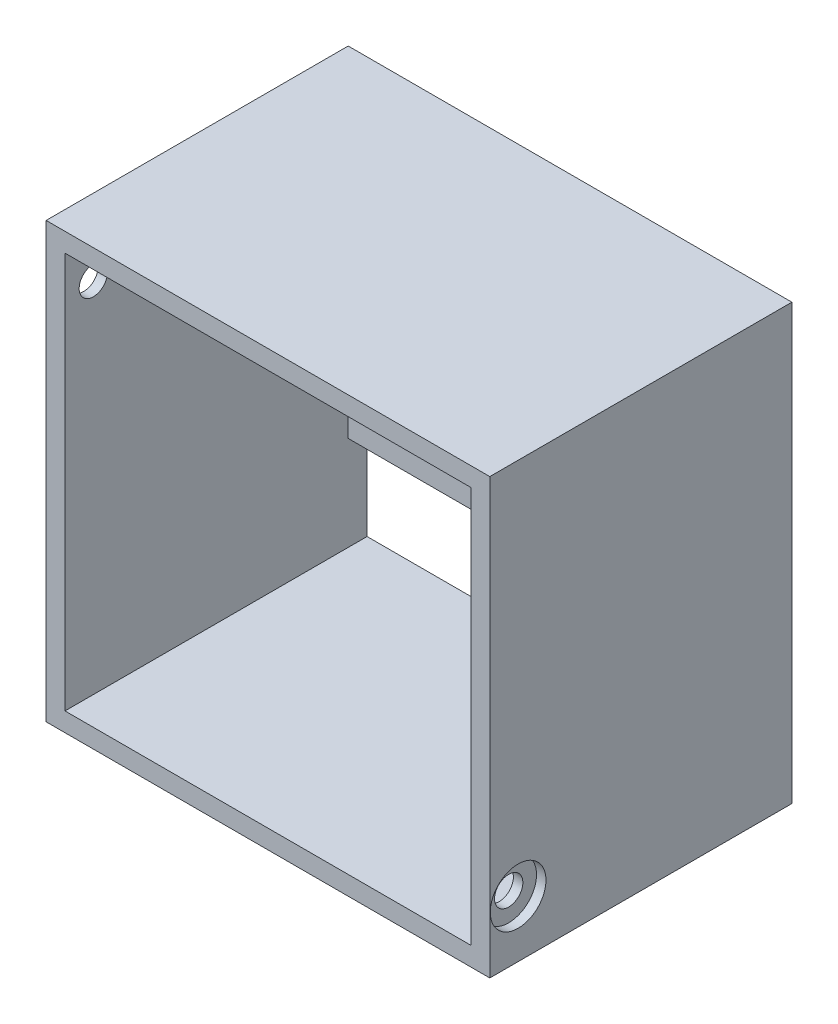
SolidWorks part; units mm, degrees
ref_plane "Front Plane" through (0, 0, 0) normal (0, 0, 1) x (1, 0, 0)
ref_plane "Top Plane" through (0, 0, 0) normal (0, 1, 0) x (1, 0, 0)
ref_plane "Right Plane" through (0, 0, 0) normal (1, 0, 0) x (0, 0, -1)
sketch "Sketch1" plane through (0, 0, 0) normal (0, 0, 1) x (1, 0, 0)
  line L1 (-39.6754, 60.7228) -> (3.3246, 60.7228)
  line L2 (-39.6754, 60.7228) -> (-39.6754, 18.7228)
  line L3 (-39.6754, 18.7228) -> (3.3246, 18.7228)
  line L4 (3.3246, 60.7228) -> (3.3246, 18.7228)
  line L9 (-41.6754, 62.7228) -> (5.3246, 62.7228)
  line L10 (-41.6754, 62.7228) -> (-41.6754, 16.7228)
  line L11 (-41.6754, 16.7228) -> (5.3246, 16.7228)
  line L12 (5.3246, 62.7228) -> (5.3246, 16.7228)
  dimension "D1" = 42
  dimension "D2" = 43
  dimension "D3" = 2
  dimension "D4" = 2
  dimension "D5" = 2
  dimension "D6" = 2
extrude "Walls" add sketch "Sketch1" along normal blind 30
extrude "Back" add sketch "Sketch1<2>" against normal blind 2 contours L4 L1 L2 L3 | L12 L9 L10 L11 L1 L4 L3 L2 region at (-18.1754, 39.7228, 0) region at (-18.1754, 62.0651, 0)
sketch "Sketch1<2>" plane through (0, 0, 0) normal (0, 0, 1) x (1, 0, 0) same geometry as "Sketch1"
sketch "Sketch2" plane through (0, 0, -2) normal (0, 0, -1) x (-1, 0, 0)
  line L0 (41.6754, 16.7228) -> (-5.3246, 16.7228) construction
  line L1 (24.6754, 28.7228) -> (39.6754, 28.7228)
  line L2 (24.6754, 28.7228) -> (24.6754, 18.7228)
  line L3 (24.6754, 18.7228) -> (39.6754, 18.7228)
  line L4 (39.6754, 28.7228) -> (39.6754, 18.7228)
  line L5 (41.6754, 62.7228) -> (41.6754, 16.7228) construction
  dimension "D1" = 10
  dimension "D2" = 15
  dimension "D3" = 2
  dimension "D4" = 2
extrude "Cable" cut sketch "Sketch2" against normal blind 2
sketch "Sketch3" plane through (-41.6754, 0, 0) normal (-1, 0, 0) x (0, 0, 1)
  line L0 (-2, 62.7228) -> (-2, 16.7228) construction
  line L1 (-2, 39.7228) -> (30, 39.7228) construction
  line L2 (30, 62.7228) -> (30, 16.7228) construction
  circle A0 centre (27, 56.7125) radius 1.5
  circle A1 centre (27, 56.7125) radius 2.95
  circle A2 centre (27, 22.733) radius 1.5
  circle A3 centre (27, 22.733) radius 2.95
  dimension "D1" = 3
  dimension "D2" = 5.9
  dimension "D3" = 29
extrude "SetScrew1" cut sketch "Sketch3" against normal blind 2 contours A0 region at (-41.6754, 56.7125, 27)
extrude "SetScrew2" cut sketch "Sketch3<6>" against normal blind 1 contours A1 A0 region at (-41.6754, 56.7125, 24.1334)
sketch "Sketch3<6>" plane through (-41.6754, 0, 0) normal (-1, 0, 0) x (0, 0, 1) same geometry as "Sketch3"
extrude "SetScrew3" cut sketch "Sketch3<7>" along normal blind 1 from surface contours A3 A2 region at (-41.6754, 22.733, 24.1334) starting at face at (5.3246, 39.7228, 14)
sketch "Sketch3<7>" plane through (-41.6754, 0, 0) normal (-1, 0, 0) x (0, 0, 1) same geometry as "Sketch3"
extrude "SetScrew4" cut sketch "Sketch3<8>" along normal blind 2 from surface contours A2 region at (-41.6754, 22.733, 27) starting at face at (5.3246, 19.783, 27)
sketch "Sketch3<8>" plane through (-41.6754, 0, 0) normal (-1, 0, 0) x (0, 0, 1) same geometry as "Sketch3"
sketch "Sketch4" plane through (0, 0, -2) normal (0, 0, -1) x (-1, 0, 0)
  line L0 (-5.3246, 39.7228) -> (41.6754, 39.7228) construction
  line L1 (-5.3246, 62.7228) -> (-5.3246, 16.7228) construction
  line L2 (41.6754, 62.7228) -> (41.6754, 16.7228) construction
  line L3 (18.1754, 62.7228) -> (18.1754, 16.7228) construction
  line L4 (41.6754, 62.7228) -> (-5.3246, 62.7228) construction
  line L5 (41.6754, 16.7228) -> (-5.3246, 16.7228) construction
  line L6 (14.1754, 34.7228) -> (22.1754, 34.7228) construction
  line L7 (14.1754, 39.7228) -> (22.1754, 39.7228)
  line L8 (14.1754, 39.7228) -> (14.1754, 29.7228)
  line L9 (14.1754, 29.7228) -> (22.1754, 29.7228)
  line L10 (22.1754, 39.7228) -> (22.1754, 29.7228)
  line L11 (18.1754, 39.7228) -> (18.1754, 29.7228) construction
  dimension "D1" = 10
  dimension "D2" = 8
extrude "Mount Joint" add sketch "Sketch4" along normal blind 15
sketch "Sketch6" plane through (-22.1754, 0, 0) normal (-1, 0, 0) x (0, 0, 1)
  line L0 (-17, 34.7228) -> (-2, 34.7228) construction
  line L1 (-17, 29.7228) -> (-17, 39.7228) construction
  line L2 (-2, 29.7228) -> (-2, 39.7228) construction
  line L3 (-12, 39.7228) -> (-12, 29.7228) construction
  line L4 (-17, 39.7228) -> (-2, 39.7228) construction
  line L5 (-17, 29.7228) -> (-2, 29.7228) construction
  circle A0 centre (-12, 34.7228) radius 2.5
  dimension "D2" = 5
  dimension "D1" = 5
extrude "Joint" cut sketch "Sketch6" against normal blind 10
